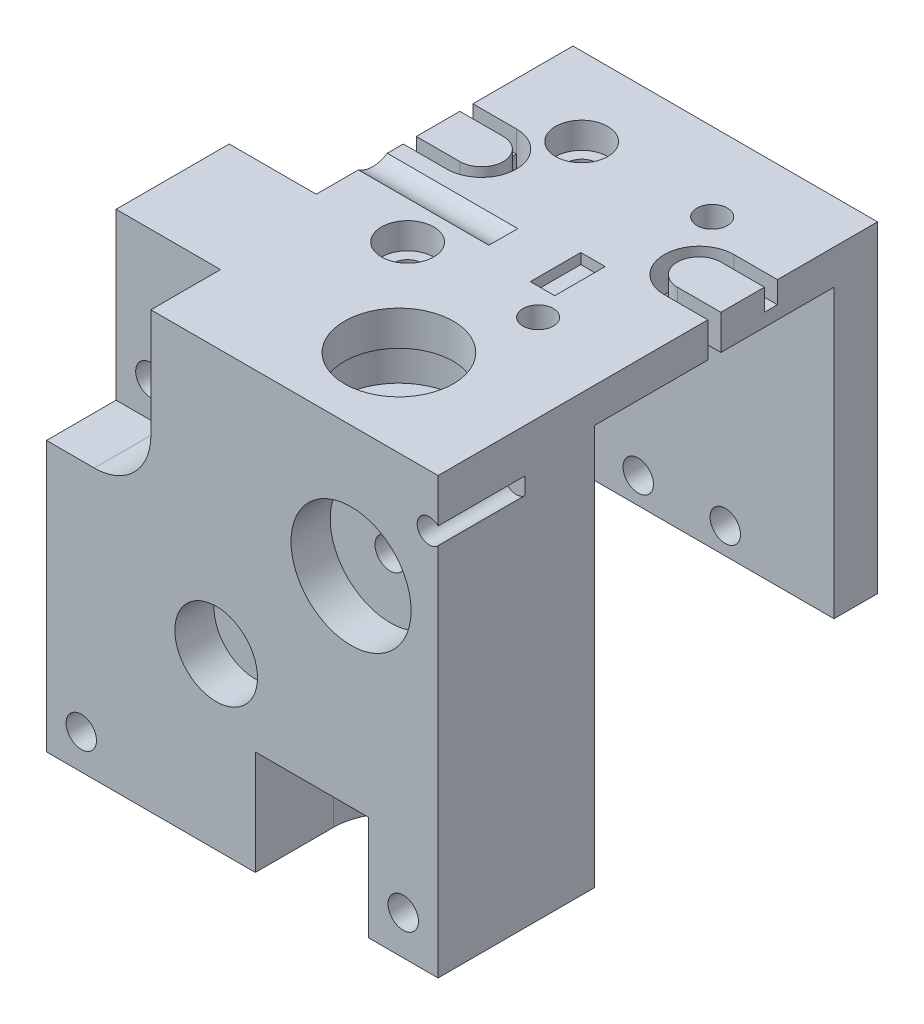
SolidWorks part; units mm, degrees
material "ABS"
ref_plane "Front Plane" through (0, 0, 0) normal (0, 0, 1) x (1, 0, 0)
ref_plane "Top Plane" through (0, 0, 0) normal (0, 1, 0) x (1, 0, 0)
ref_plane "Right Plane" through (0, 0, 0) normal (1, 0, 0) x (0, 0, -1)
sketch "Sketch1" plane through (0, 0, 0) normal (0, 1, 0) x (1, 0, 0)
  line L1 (-17.5, -14) -> (17.5, -14)
  line L2 (-17.5, -14) -> (-17.5, 14)
  line L3 (-17.5, 14) -> (17.5, 14)
  line L4 (17.5, -14) -> (17.5, 14)
  line L5 (-17.5, -14) -> (17.5, 14) construction
  line L6 (-17.5, 14) -> (17.5, -14) construction
  point P0 (0, 0)
  dimension "D1" = 28
  dimension "D2" = 35
extrude "Boss-Extrude1" add sketch "Sketch1" along normal blind 4
sketch "Sketch2" plane through (0, 4, 0) normal (0, 1, 0) x (1, 0, 0)
  line L0 (-17.5, -14) -> (17.5, -14) construction
  line L1 (-17.5, 14) -> (-17.5, -14) construction
  line L2 (-17.5, -14) -> (17.5, -14) construction
  line L3 (17.5, 14) -> (-17.5, 14) construction
  circle A0 centre (-7.5, -10) radius 1.75
  circle A1 centre (-7.5, 10) radius 1.75
  circle A2 centre (7.5, -10) radius 1.75
  circle A3 centre (7.5, 10) radius 1.75
  dimension "D1" = 3.5
  dimension "D2" = 3.5
  dimension "D5" = 3.5
  dimension "D8" = 3.5
  dimension "D3" = 20
  dimension "D4" = 4
  dimension "D6" = 15
  dimension "D7" = 10
  dimension "D9" = 15
  dimension "D10" = 4
  dimension "D11" = 4
extrude "Cut-Extrude1" cut sketch "Sketch2" against normal through all
sketch "Sketch3" plane through (0, 0, 14) normal (0, 0, 1) x (1, 0, 0)
  line L0 (17.5, 4) -> (17.5, 0) construction
  line L1 (-17.5, 4) -> (17.5, 4)
  line L2 (-17.5, 4) -> (-17.5, -46)
  line L3 (-17.5, -46) -> (17.5, -46)
  line L4 (17.5, 4) -> (17.5, -46)
  dimension "D1" = 50
extrude "Boss-Extrude2" add sketch "Sketch3" along normal blind 17.5 and the other way blind 0.5
sketch "Sketch7" plane through (0, 0, -14) normal (0, 0, -1) x (-1, 0, 0)
  line L1 (-17.5, 4) -> (17.5, 4)
  line L2 (-17.5, 4) -> (-17.5, -33)
  line L3 (-17.5, -33) -> (17.5, -33)
  line L4 (17.5, 4) -> (17.5, -33)
  line L6 (17.5, 4) -> (17.5, 0) construction
  dimension "D1" = 37
extrude "Boss-Extrude3" add sketch "Sketch7" along normal blind 5
sketch "Sketch10" plane through (0, 0, -19) normal (0, 0, -1) x (-1, 0, 0)
  line L1 (0, 4) -> (0, -33) construction
  line L3 (17.5, 4) -> (-17.5, 4) construction
  line L4 (-17.5, -33) -> (17.5, -33) construction
  circle A1 centre (-5, -30) radius 1.75
  circle A2 centre (5, -30) radius 1.75
  dimension "D1" = 3
  dimension "D2" = 3.5
  dimension "D4" = 3.5
  dimension "D3" = 5
  dimension "D5" = 5
extrude "Cut-Extrude6" cut sketch "Sketch10" against normal blind 5
sketch "Sketch18" plane through (0, 4, 0) normal (0, 1, 0) x (1, 0, 0)
  line L0 (-17.5, -10) -> (-10.5, -10)
  line L1 (-17.5, 19) -> (-17.5, -31.5) construction
  line L2 (-10.5, -10) -> (-10.5, -11.5)
  line L3 (-10.5, -11.5) -> (-17.5, -11.5)
  line L4 (-17.5, -11.5) -> (-17.5, -10)
  line L5 (17.5, 10) -> (10.5, 10)
  line L6 (17.5, -31.5) -> (17.5, 19) construction
  line L7 (10.5, 10) -> (10.5, 11.5)
  line L8 (10.5, 11.5) -> (17.5, 11.5)
  line L9 (17.5, 11.5) -> (17.5, 10)
  circle A0 centre (-7.5, -10) radius 1.75 construction
  circle A1 centre (7.5, 10) radius 1.75 construction
  dimension "D4" = 3
  dimension "D1" = 0
  dimension "D2" = 3
  dimension "D3" = 1.5
  dimension "D5" = 0
  dimension "D6" = 1.5
extrude "Cut-Extrude14" [suppressed] cut sketch "Sketch18" against normal through all
sketch "Sketch19" plane through (0, 4, 0) normal (0, 1, 0) x (1, 0, 0)
  line L0 (-17.5, 19) -> (-17.5, -31.5) construction
  line L1 (17.5, -31.5) -> (17.5, 19) construction
  circle A0 centre (-7.5, 0) radius 1.75
  circle A1 centre (7.5, 0) radius 1.75
  dimension "D3" = 3.5
  dimension "D4" = 3.5
  dimension "D1" = 10
  dimension "D2" = 10
extrude "Cut-Extrude15" [suppressed] cut sketch "Sketch19" against normal through all
sketch "Sketch20" [suppressed] plane through (0, 0, 0) normal (0, -1, 0) x (1, 0, 0)
  line L1 (10.9641, 0) -> (9.2321, 3)
  line L2 (9.2321, 3) -> (5.7679, 3)
  line L3 (5.7679, 3) -> (4.0359, 0)
  line L4 (4.0359, 0) -> (5.7679, -3)
  line L5 (5.7679, -3) -> (9.2321, -3)
  line L6 (9.2321, -3) -> (10.9641, 0)
  line L7 (-10.9641, 0) -> (-9.2321, -3)
  line L8 (-9.2321, -3) -> (-5.7679, -3)
  line L9 (-5.7679, -3) -> (-4.0359, 0)
  line L10 (-4.0359, 0) -> (-5.7679, 3)
  line L11 (-5.7679, 3) -> (-9.2321, 3)
  line L12 (-9.2321, 3) -> (-10.9641, 0)
  circle A0 centre (7.5, 0) radius 3 construction
  circle A1 centre (-7.5, 0) radius 3 construction
  dimension "D1" = 6
  dimension "D2" = 6
extrude "Cut-Extrude16" [suppressed] cut sketch "Sketch20" against normal blind 3
sketch "Sketch21" [suppressed] plane through (0, 4, 0) normal (0, 1, 0) x (1, 0, 0)
  line L0 (-10.5, -10) -> (-17.5, -10) construction
  circle A0 centre (-17, -10) radius 0.5
  dimension "D1" = 1
extrude "Cut-Extrude17" [suppressed] cut sketch "Sketch21" against normal blind 4
pattern_linear "LPattern2" [suppressed] count 4 spacing 2 of bodies 121
fillet "Fillet2" [suppressed] radius 0.15
sketch "Sketch24" plane through (-17.5, 0, 0) normal (-1, 0, 0) x (0, 0, 1)
  line L5 (31.5, -46) -> (13.5, -46) construction
  line L6 (13.5, -46) -> (31.5, -46)
  line L7 (13.5, -46) -> (13.5, 0)
  line L8 (13.5, 0) -> (31.5, 0)
  line L9 (31.5, -46) -> (31.5, 0)
  line L10 (13.5, 0) -> (13.5, -46) construction
  line L11 (31.5, 4) -> (31.5, -46) construction
extrude "Boss-Extrude4" add sketch "Sketch24" along normal blind 10
sketch "Sketch37" plane through (-17.5, 0, 0) normal (-1, 0, 0) x (0, 0, 1)
  line L1 (10.5, 4) -> (23.5, 4)
  line L2 (10.5, 4) -> (10.5, -10)
  line L3 (10.5, -10) -> (23.5, -10)
  line L4 (23.5, 4) -> (23.5, -10)
  dimension "D1" = 3
  dimension "D2" = 10
  dimension "D3" = 14
extrude "Boss-Extrude9" add sketch "Sketch37" along normal blind 10
sketch "Sketch22" plane through (0, 0, 31.5) normal (0, 0, 1) x (1, 0, 0)
  line L0 (-27.5, -46) -> (-27.5, 0) construction
  line L1 (-15.5, 0) -> (-27.5, 0)
  line L2 (-27.5, -46) -> (17.5, -46) construction
  line L4 (-27.5, 0) -> (-17.5, 0) construction
  line L5 (-27.5, -46) -> (17.5, -46) construction
  line L6 (-27.5, 0) -> (-27.5, -15)
  line L9 (-27.5, -15) -> (-22, -15)
  line L10 (-15.5, 0) -> (-15.5, -8.5)
  line L11 (9.5, -46) -> (-3.5, -46)
  line L12 (9.5, -46) -> (9.5, -34)
  line L13 (9.5, -34) -> (-3.5, -34)
  line L14 (-3.5, -46) -> (-3.5, -34)
  line L16 (-15.5, 0) -> (-17.5, 0)
  line L17 (-15.5, 0) -> (-15.5, 4)
  line L18 (-15.5, 4) -> (-17.5, 4)
  line L19 (-17.5, 0) -> (-17.5, 4)
  circle A0 centre (-23.5, -42) radius 1.75
  circle A1 centre (13.5, -41.5) radius 1.75
  circle A3 centre (7.5, -11) radius 6.9
  circle A4 centre (-8, -26.5) radius 4.75
  arc A5 (-22, -15) -> (-15.5, -8.5) centre (-22, -8.5) ccw
  circle A6 centre (7.5, -11) radius 1.75
  circle A7 centre (-23.5, -11) radius 1.75
  point P21 (-15.5, -15)
  line M3 (-17.5, 4) -> (-17.5, 0)
  line M6 (17.5, 4) -> (-17.5, 4)
  line M24 (-17.5, 0) -> (-27.5, 0)
  line M25 (-27.5, 0) -> (-27.5, -46)
  dimension "D3" = 3.5
  dimension "D6" = 35
  dimension "D7" = 3.5
  dimension "D9" = 13.8
  dimension "D11" = 9.5
  dimension "D15" = 6.5
  dimension "D22" = 3.5
  dimension "D23" = 3.5
  dimension "D2" = 4
  dimension "D4" = 4.5
  dimension "D5" = 4
  dimension "D8" = 12
  dimension "D10" = 35
  dimension "D12" = 19.5
  dimension "D13" = 19.5
  dimension "D14" = 31
  dimension "D16" = 24
  dimension "D17" = 13
  dimension "D18" = 12
  dimension "D19" = 41
  dimension "D20" = 4
  dimension "D21" = 35
extrude "Cut-Extrude19" cut sketch "Sketch22" against normal up to next contours A0 | A1 | A7 | A6 region at (-23.5, -42, 31.5) region at (13.5, -41.5, 31.5) region at (7.5, -11, 31.5) region at (-23.5, -11, 31.5)
extrude "Cut-Extrude20" cut sketch "Sketch22<3>" against normal blind 4.5 contours A3 | A4
sketch "Sketch22<3>" plane through (0, 0, 31.5) normal (0, 0, 1) x (1, 0, 0) same geometry as "Sketch22"
extrude "Cut-Extrude24" cut sketch "Sketch22<5>" against normal blind 8 contours L9 A5 L10 L1 A7 M24 M25 | L1 L17 M6 M3 region at (-21.6364, -6.9513, 31.5) region at (-16.5, 2, 31.5)
sketch "Sketch22<5>" plane through (0, 0, 31.5) normal (0, 0, 1) x (1, 0, 0) same geometry as "Sketch22"
extrude "Cut-Extrude21" cut sketch "Sketch22<4>" against normal blind 15.5 contours L14 L13 L12 L11
sketch "Sketch22<4>" plane through (0, 0, 31.5) normal (0, 0, 1) x (1, 0, 0) same geometry as "Sketch22"
fillet "Fillet3" radius 6.5 2 edges at (9.5, -40, 16) (-3.5, -40, 16)
sketch "Sketch26" plane through (0, -34, 0) normal (0, -1, 0) x (1, 0, 0)
  line L0 (9.5, 31.5) -> (-3.5, 31.5) construction
  line L1 (-3.5, 22.5) -> (-3.5, 31.5) construction
  circle A0 centre (3, 21.5) radius 2.25
  dimension "D1" = 4.5
  dimension "D2" = 10
  dimension "D3" = 6.5
extrude "Cut-Extrude22" cut sketch "Sketch26" against normal through all
sketch "Sketch27" plane through (0, 4, 0) normal (0, 1, 0) x (1, 0, 0)
  circle A0 centre (3, -21.5) radius 6.25
  dimension "D1" = 12.5
extrude "Cut-Extrude23" cut sketch "Sketch27" against normal blind 8
sketch "Sketch29" plane through (0, 0, 13.5) normal (0, 0, -1) x (-1, 0, 0)
  line L1 (-4.1514, -11) -> (-5.8257, -8.1)
  line L2 (-5.8257, -8.1) -> (-9.1743, -8.1)
  line L3 (-9.1743, -8.1) -> (-10.8486, -11)
  line L4 (-10.8486, -11) -> (-9.1743, -13.9)
  line L5 (-9.1743, -13.9) -> (-5.8257, -13.9)
  line L6 (-5.8257, -13.9) -> (-4.1514, -11)
  line L7 (20.1514, -11) -> (21.8257, -13.9)
  line L8 (21.8257, -13.9) -> (25.1743, -13.9)
  line L9 (25.1743, -13.9) -> (26.8486, -11)
  line L10 (26.8486, -11) -> (25.1743, -8.1)
  line L11 (25.1743, -8.1) -> (21.8257, -8.1)
  line L12 (21.8257, -8.1) -> (20.1514, -11)
  line L13 (-10.1514, -41.5) -> (-11.8257, -38.6)
  line L14 (-11.8257, -38.6) -> (-15.1743, -38.6)
  line L15 (-15.1743, -38.6) -> (-16.8486, -41.5)
  line L16 (-16.8486, -41.5) -> (-15.1743, -44.4)
  line L17 (-15.1743, -44.4) -> (-11.8257, -44.4)
  line L18 (-11.8257, -44.4) -> (-10.1514, -41.5)
  line L25 (23.5, -45.3486) -> (26.4, -43.6743)
  line L26 (26.4, -43.6743) -> (26.4, -40.3257)
  line L27 (26.4, -40.3257) -> (23.5, -38.6514)
  line L28 (23.5, -38.6514) -> (20.6, -40.3257)
  line L29 (20.6, -40.3257) -> (20.6, -43.6743)
  line L30 (20.6, -43.6743) -> (23.5, -45.3486)
  circle A0 centre (-7.5, -11) radius 2.9 construction
  circle A1 centre (23.5, -11) radius 2.9 construction
  circle A2 centre (-13.5, -41.5) radius 2.9 construction
  circle A3 centre (23.5, -42) radius 2.9 construction
  dimension "D1" = 5.8
  dimension "D2" = 5.8
  dimension "D3" = 5.8
  dimension "D4" = 5.8
extrude "Cut-Extrude25" cut sketch "Sketch29" against normal blind 3 and the other way blind 3
sketch "Sketch30" plane through (0, 4, 0) normal (0, 1, 0) x (1, 0, 0)
  circle A0 centre (-7.5, 10) radius 3
  circle A1 centre (-7.5, -10) radius 3
  dimension "D1" = 6
  dimension "D2" = 6
extrude "Cut-Extrude26" cut sketch "Sketch30" against normal blind 3
sketch "Sketch31" plane through (0, 4, 0) normal (0, 1, 0) x (1, 0, 0)
  line L0 (-17.5, 0) -> (17.5, 0) construction
  line L1 (-17.5, 19) -> (-17.5, -10.5) construction
  line L2 (17.5, -31.5) -> (17.5, 19) construction
  line L4 (-17.5, 1) -> (-12.5, 1)
  line L10 (-17.5, -0.5) -> (-12.5, -0.5)
  line L11 (-17.5, 1) -> (-17.5, -0.5)
  line L12 (-12.5, 6) -> (-12.5, 7.5)
  arc A0 (-12.5, 1) -> (-12.5, 6) centre (-12.5, 3.5) ccw
  arc A2 (-12.5, -0.5) -> (-12.5, 7.5) centre (-12.5, 3.5) ccw
  dimension "D4" = 2.5
  dimension "D1" = 1
  dimension "D2" = 1.5
  dimension "D3" = 5
extrude "Cut-Extrude27" cut sketch "Sketch31" against normal through all
sketch "Sketch32" plane through (0, 4, 0) normal (0, 1, 0) x (1, 0, 0)
  line L0 (-17.5, 19) -> (-17.5, 1) construction
  line L1 (-12.5, 7.5) -> (-17.5, 7.5)
  line L2 (-12.5, 7.5) -> (-12.5, 6)
  line L3 (-12.5, 6) -> (-17.5, 6)
  line L4 (-17.5, 7.5) -> (-17.5, 6)
  arc A0 (-12.5, -0.5) -> (-12.5, 7.5) centre (-12.5, 3.5) ccw construction
extrude "Cut-Extrude28" cut sketch "Sketch32" against normal blind 2.5
sketch "Sketch33" plane through (-17.5, 0, 0) normal (-1, 0, 0) x (0, 0, 1)
  line L0 (0.5, 0) -> (0.5, 4) construction
  line L1 (0.5, 4) -> (10.5, 4) construction
  circle A0 centre (4, 6.5) radius 3
  dimension "D3" = 6
  dimension "D1" = 3.5
  dimension "D2" = 2.5
extrude "Cut-Extrude29" cut sketch "Sketch33" against normal blind 15
sketch "Sketch34" plane through (0, 4, 0) normal (0, 1, 0) x (1, 0, 0)
  line L1 (3.5, -6.9) -> (6.3, -6.9)
  line L2 (3.5, -6.9) -> (3.5, -1.1)
  line L3 (3.5, -1.1) -> (6.3, -1.1)
  line L4 (6.3, -6.9) -> (6.3, -1.1)
  circle A0 centre (7.5, -10) radius 1.75 construction
  dimension "D1" = 2.8
  dimension "D2" = 5.8
  dimension "D3" = 3.1
  dimension "D4" = 1.2
extrude "Cut-Extrude30" cut sketch "Sketch34" against normal blind 1.2
ref_plane "Plane1" through (0, 0, 0) normal (-1, 0, 0) x (0, 0, 1)
mirror "Mirror1" about plane through (0, 0, 0) normal (-1, 0, 0) of "Cut-Extrude28", "Cut-Extrude27"
sketch "Sketch38" plane through (0, -4, 0) normal (0, 1, 0) x (1, 0, 0)
  circle A0 centre (3, -21.5) radius 7
  dimension "D1" = 14
extrude "Cut-Extrude31" cut sketch "Sketch38" along normal blind 4
sketch "Sketch39" plane through (-27.5, 0, 0) normal (-1, 0, 0) x (0, 0, 1)
  line L0 (13.5, -46) -> (17, -46)
  line L1 (13.5, -46) -> (31.5, -46) construction
  line L2 (13.5, -46) -> (13.5, -19)
  line L3 (13.5, -10) -> (13.5, -46) construction
  line L4 (13.5, -19) -> (17, -19)
  line L5 (20.5, -22.5) -> (20.5, -26)
  line L6 (20.5, -26) -> (27.5, -26)
  line L7 (27.5, -26) -> (27.5, -39)
  line L8 (27.5, -39) -> (20.5, -39)
  line L9 (20.5, -39) -> (20.5, -42.5)
  line L11 (27.5, -29) -> (23.5, -29)
  line L12 (27.5, -29) -> (27.5, -36)
  line L13 (27.5, -36) -> (23.5, -36)
  line L14 (23.5, -29) -> (23.5, -36)
  line L15 (13.5, -26) -> (18.5, -26)
  line L16 (13.5, -26) -> (13.5, -39)
  line L17 (13.5, -39) -> (18.5, -39)
  line L18 (18.5, -26) -> (18.5, -39)
  arc A0 (17, -46) -> (20.5, -42.5) centre (17, -42.5) ccw
  arc A1 (17, -19) -> (20.5, -22.5) centre (17, -22.5) cw
  point P15 (20.5, -46)
  point P18 (20.5, -19)
  dimension "D7" = 3.5
  dimension "D1" = 7
  dimension "D2" = 27
  dimension "D3" = 7
  dimension "D4" = 7
  dimension "D5" = 7
  dimension "D6" = 13
  dimension "D8" = 4
  dimension "D9" = 7
  dimension "D10" = 3
  dimension "D11" = 5
extrude "Cut-Extrude32" cut sketch "Sketch39" against normal blind 3 contours L18 L15 L2 L17 | L11 L14 L13 L7 region at (-27.5, -32.5, 16) region at (-27.5, -32.5, 25.5)
sketch "Sketch40" plane through (-27.5, 0, 0) normal (-1, 0, 0) x (0, 0, 1)
  line L0 (13.5, -10) -> (13.5, -26) construction
  line L1 (13.5, -46) -> (31.5, -46) construction
  circle A0 centre (17, -22.5) radius 1.4
  dimension "D3" = 2.8
  dimension "D1" = 3.5
  dimension "D2" = 23.5
extrude "Cut-Extrude33" cut sketch "Sketch40" against normal blind 15
sketch "Sketch41" plane through (-27.5, 0, 0) normal (-1, 0, 0) x (0, 0, 1)
  line L0 (13.5, -39) -> (13.5, -46) construction
  line L1 (13.5, -46) -> (31.5, -46) construction
  line L2 (20.5, -42.5) -> (20.5, -39)
  line L15 (23, -42.5) -> (23, -39)
  line L16 (17, -46) -> (17, -48.5)
  line L17 (20.5, -39) -> (23, -39)
  line L18 (17, -46) -> (21.8734, -46)
  circle A0 centre (17, -42.5) radius 1.25
  arc A1 (17, -46) -> (20.5, -42.5) centre (17, -42.5) ccw
  arc A2 (17, -48.5) -> (23, -42.5) centre (17, -42.5) ccw
  line M16 (13.5, -46) -> (31.5, -46)
  dimension "D5" = 2.5
  dimension "D1" = 3.5
  dimension "D2" = 3.5
  dimension "D3" = 3.5
  dimension "D4" = 2.5
extrude "Boss-Extrude10" add sketch "Sketch41" along normal blind 2.5 contours A0 | A2 L15 L17 L2 A1 M16 region at (-27.5, -42.7022, 21.4056) region at (-27.5, -42.5, 17)
sketch "Sketch42" plane through (0, 0, 31.5) normal (0, 0, 1) x (1, 0, 0)
  circle A0 centre (16.5, -2) radius 1.4
  circle A1 centre (-23.5, -42) radius 1.75 construction
  dimension "D3" = 2.8
  dimension "D1" = 40
  dimension "D2" = 40
extrude "Cut-Extrude34" cut sketch "Sketch42" against normal blind 10
